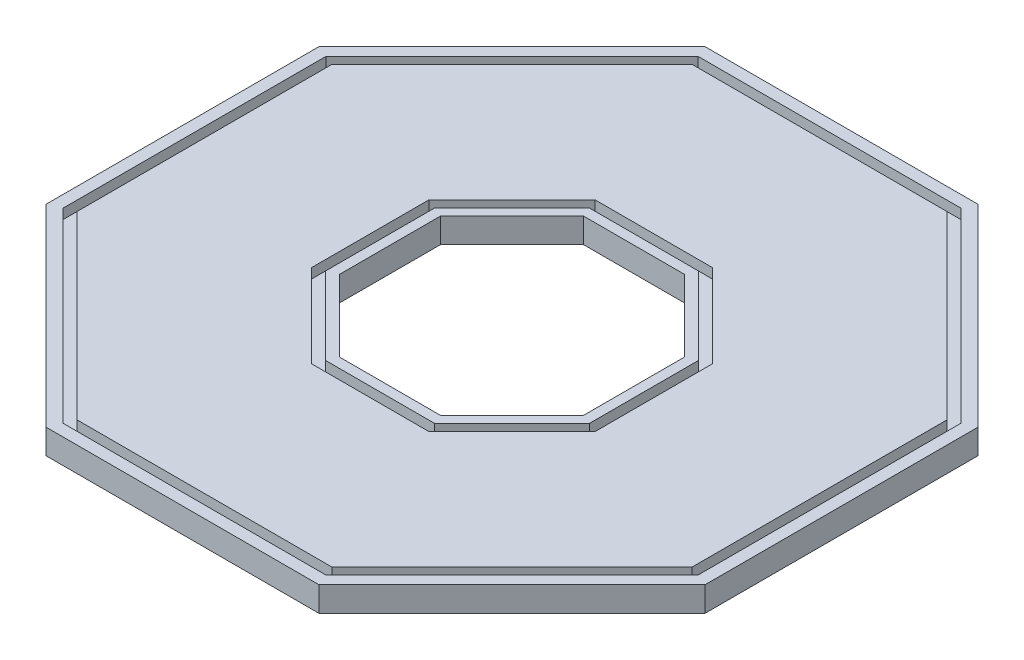
SolidWorks part; units mm, degrees
ref_plane "정면" through (0, 0, 0) normal (0, 0, 1) x (1, 0, 0)
ref_plane "윗면" through (0, 0, 0) normal (0, 1, 0) x (1, 0, 0)
ref_plane "우측면" through (0, 0, 0) normal (1, 0, 0) x (0, 0, -1)
sketch "스케치1" plane through (0, 0, 0) normal (0, 1, 0) x (1, 0, 0)
  line L0 (-55, 0) -> (55, 0) construction
  line L1 (13.3624, -32.2597) -> (32.2597, -13.3624)
  line L2 (32.2597, -13.3624) -> (32.2597, 13.3624)
  line L3 (32.2597, 13.3624) -> (13.3624, 32.2597)
  line L4 (13.3624, 32.2597) -> (-13.3624, 32.2597)
  line L5 (-13.3624, 32.2597) -> (-32.2597, 13.3624)
  line L6 (-32.2597, 13.3624) -> (-32.2597, -13.3624)
  line L7 (-32.2597, -13.3624) -> (-13.3624, -32.2597)
  line L8 (-13.3624, -32.2597) -> (13.3624, -32.2597)
  line L9 (13.7766, -33.2597) -> (33.2597, -13.7766)
  line L10 (33.2597, -13.7766) -> (33.2597, 13.7766)
  line L11 (33.2597, 13.7766) -> (13.7766, 33.2597)
  line L12 (13.7766, 33.2597) -> (-13.7766, 33.2597)
  line L13 (-13.7766, 33.2597) -> (-33.2597, 13.7766)
  line L14 (-33.2597, 13.7766) -> (-33.2597, -13.7766)
  line L15 (-33.2597, -13.7766) -> (-13.7766, -33.2597)
  line L16 (-13.7766, -33.2597) -> (13.7766, -33.2597)
  line L17 (12.9482, -31.2597) -> (31.2597, -12.9482)
  line L18 (31.2597, -12.9482) -> (31.2597, 12.9482)
  line L19 (31.2597, 12.9482) -> (12.9482, 31.2597)
  line L20 (12.9482, 31.2597) -> (-12.9482, 31.2597)
  line L21 (-12.9482, 31.2597) -> (-31.2597, 12.9482)
  line L22 (-31.2597, 12.9482) -> (-31.2597, -12.9482)
  line L23 (-31.2597, -12.9482) -> (-12.9482, -31.2597)
  line L24 (-12.9482, -31.2597) -> (12.9482, -31.2597)
  circle A0 centre (0, 0) radius 34.9176 construction
  dimension "D1" = 72
  dimension "D2" = 1
  dimension "D3" = 1
extrude "보스-돌출1" add sketch "스케치1" along normal blind 2.5 contours L23 L24 L17 L18 L19 L20 L21 L22 | L7 L8 L1 L2 L3 L4 L5 L6 L24 L23 L22 L21 L20 L19 L18 L17 | L15 L16 L9 L10 L11 L12 L13 L14 L8 L7 L6 L5 L4 L3 L2 L1 region at (0, 0, 31.3472) region at (0, 0, 32.3189) region at (0, 0, 0)
sketch "스케치2" plane through (0, 2.5, 0) normal (0, 1, 0) x (1, 0, 0)
  line L0 (33.2597, -13.7766) -> (33.2597, 13.7766) construction
  line L1 (13.2791, -32.0586) -> (32.0586, -13.2791)
  line L2 (32.0586, -13.2791) -> (32.0586, 13.2791)
  line L3 (32.0586, 13.2791) -> (13.2791, 32.0586)
  line L4 (13.2791, 32.0586) -> (-13.2791, 32.0586)
  line L5 (-13.2791, 32.0586) -> (-32.0586, 13.2791)
  line L6 (-32.0586, 13.2791) -> (-32.0586, -13.2791)
  line L7 (-32.0586, -13.2791) -> (-13.2791, -32.0586)
  line L8 (-13.2791, -32.0586) -> (13.2791, -32.0586)
  line L9 (12.8649, -31.0586) -> (31.0586, -12.8649)
  line L10 (31.0586, -12.8649) -> (31.0586, 12.8649)
  line L11 (31.0586, 12.8649) -> (12.8649, 31.0586)
  line L12 (12.8649, 31.0586) -> (-12.8649, 31.0586)
  line L13 (-12.8649, 31.0586) -> (-31.0586, 12.8649)
  line L14 (-31.0586, 12.8649) -> (-31.0586, -12.8649)
  line L15 (-31.0586, -12.8649) -> (-12.8649, -31.0586)
  line L16 (-12.8649, -31.0586) -> (12.8649, -31.0586)
  circle A0 centre (0, 0) radius 34.7 construction
  dimension "D1" = 69.4
  dimension "D2" = 1
extrude "컷-돌출1" cut sketch "스케치2" against normal blind 1
sketch "스케치4" plane through (0, 2.5, 0) normal (0, 1, 0) x (1, 0, 0)
  line L0 (31.0586, -12.8649) -> (31.0586, 12.8649) construction
  line L1 (5.9316, -14.3201) -> (14.3201, -5.9316)
  line L2 (14.3201, -5.9316) -> (14.3201, 5.9316)
  line L3 (14.3201, 5.9316) -> (5.9316, 14.3201)
  line L4 (5.9316, 14.3201) -> (-5.9316, 14.3201)
  line L5 (-5.9316, 14.3201) -> (-14.3201, 5.9316)
  line L6 (-14.3201, 5.9316) -> (-14.3201, -5.9316)
  line L7 (-14.3201, -5.9316) -> (-5.9316, -14.3201)
  line L8 (-5.9316, -14.3201) -> (5.9316, -14.3201)
  line L9 (5.5174, -13.3201) -> (13.3201, -5.5174)
  line L10 (13.3201, -5.5174) -> (13.3201, 5.5174)
  line L11 (13.3201, 5.5174) -> (5.5174, 13.3201)
  line L12 (5.5174, 13.3201) -> (-5.5174, 13.3201)
  line L13 (-5.5174, 13.3201) -> (-13.3201, 5.5174)
  line L14 (-13.3201, 5.5174) -> (-13.3201, -5.5174)
  line L15 (-13.3201, -5.5174) -> (-5.5174, -13.3201)
  line L16 (-5.5174, -13.3201) -> (5.5174, -13.3201)
  line L17 (5.1032, -12.3201) -> (12.3201, -5.1032)
  line L18 (12.3201, -5.1032) -> (12.3201, 5.1032)
  line L19 (12.3201, 5.1032) -> (5.1032, 12.3201)
  line L20 (5.1032, 12.3201) -> (-5.1032, 12.3201)
  line L21 (-5.1032, 12.3201) -> (-12.3201, 5.1032)
  line L22 (-12.3201, 5.1032) -> (-12.3201, -5.1032)
  line L23 (-12.3201, -5.1032) -> (-5.1032, -12.3201)
  line L24 (-5.1032, -12.3201) -> (5.1032, -12.3201)
  circle A0 centre (0, 0) radius 15.5 construction
  dimension "D1" = 31
  dimension "D2" = 1
  dimension "D3" = 1
extrude "컷-돌출2" cut sketch "스케치4" against normal blind 3.8 contours L23 L24 L17 L18 L19 L20 L21 L22 region at (0, 2.5, 0)
extrude "컷-돌출3" cut sketch "스케치4<3>" against normal blind 1 contours L7 L8 L1 L2 L3 L4 L5 L6 L16 L15 L14 L13 L12 L11 L10 L9 region at (0, 2.5, 13.9151)
sketch "스케치4<3>" plane through (0, 2.5, 0) normal (0, 1, 0) x (1, 0, 0) same geometry as "스케치4"
